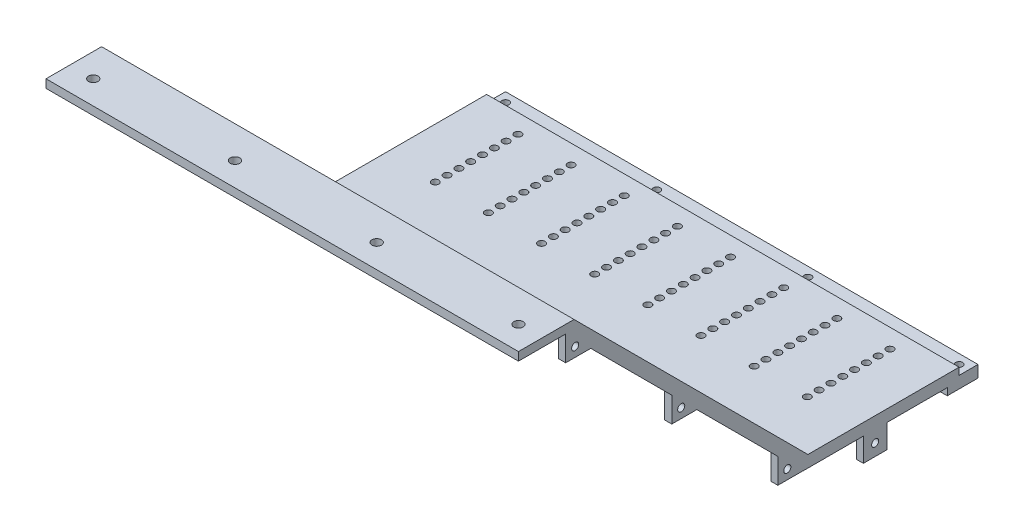
SolidWorks part; units mm, degrees
ref_plane "Front Plane" through (0, 0, 0) normal (0, 0, 1) x (1, 0, 0)
ref_plane "Top Plane" through (0, 0, 0) normal (0, 1, 0) x (1, 0, 0)
ref_plane "Right Plane" through (0, 0, 0) normal (1, 0, 0) x (0, 0, -1)
sketch "Sketch4" plane through (0, 0, 0) normal (1, 0, 0) x (0, 0, -1)
  line L0 (0, 0) -> (-8, 0)
  line L1 (-8, 0) -> (-8, 3)
  line L2 (-8, 3) -> (-72, 3)
  line L3 (-72, 3) -> (-170.9949, 101.9949)
  dimension "D1" = 8
  dimension "D2" = 3
  dimension "D3" = 64
  dimension "D4" = 135
  dimension "D5" = 140
extrude "Extrude-Thin2" add sketch "Sketch4" along normal blind 200 thin thin type one direction reverse wall 5
sketch "Sketch6" plane through (0, 3, 0) normal (0, 1, 0) x (1, 0, 0)
  line L0 (200, -8) -> (200, -72) construction
  line L1 (200, -8) -> (0, -8) construction
  circle A0 centre (178.75, -16) radius 1.5
  dimension "D1" = 3
  dimension "D2" = 21.25
  dimension "D3" = 8
extrude "Cut-Extrude2" cut sketch "Sketch6" against normal up to next
pattern_linear "LPattern1" count 8 spacing 5 along (0, 0, 1) count 8 spacing 22.5 along (-1, 0, 0) of "Cut-Extrude2"
sketch "Sketch7" plane through (0, 0, 0) normal (0, 1, 0) x (1, 0, 0)
  line L0 (200, 0) -> (0, 0) construction
  line L1 (200, 0) -> (200, -8) construction
  circle A0 centre (196, -4) radius 1.5
  dimension "D1" = 3
  dimension "D2" = 4
  dimension "D3" = 4
extrude "Cut-Extrude3" cut sketch "Sketch7" against normal up to next
pattern_linear "LPattern2" count 4 spacing 64 along (-1, 0, 0) of "Cut-Extrude3"
sketch "Sketch8" plane through (0, -34.5, 34.5) normal (0, 0.7071, -0.7071) x (1, 0, 0)
  line L0 (0, -53.033) -> (0, -193.033) construction
  line L1 (17.5, -176.033) -> (182.5, -176.033)
  line L2 (17.5, -176.033) -> (17.5, -70.033)
  line L3 (17.5, -70.033) -> (182.5, -70.033)
  line L4 (182.5, -176.033) -> (182.5, -70.033)
  line L5 (17.5, -176.033) -> (182.5, -70.033) construction
  line L6 (17.5, -70.033) -> (182.5, -176.033) construction
  line L7 (200, -53.033) -> (0, -53.033) construction
  circle A0 centre (19, -180.533) radius 1.5
  circle A1 centre (19, -65.533) radius 1.5
  circle A2 centre (181, -65.533) radius 1.5
  circle A3 centre (181, -180.533) radius 1.5
  point P0 (100, -123.033)
  dimension "D5" = 3
  dimension "D6" = 3
  dimension "D10" = 3
  dimension "D11" = 3
  dimension "D1" = 165
  dimension "D2" = 100
  dimension "D3" = 106
  dimension "D4" = 70
  dimension "D7" = 115
  dimension "D8" = 57.5
  dimension "D9" = 1.5
  dimension "D12" = 1.5
extrude "Cut-Extrude4" cut sketch "Sketch8" against normal up to next
sketch "Sketch9" plane through (200, 0, 0) normal (1, 0, 0) x (0, 0, -1)
  line L0 (-170.9949, 101.9949) -> (-174.5305, 101.9949)
  line L1 (-174.5305, 101.9949) -> (-174.5305, 98.4594)
  line L2 (-174.5305, 98.4594) -> (-170.9949, 101.9949)
extrude "Boss-Extrude1" add sketch "Sketch9" against normal up to surface (200 mm away) up to face at (0, 19.2454, 53.3597)
sketch "Sketch10" plane through (0, 0, 174.5305) normal (0, 0, 1) x (1, 0, 0)
  line L1 (0, 101.9949) -> (200, 101.9949)
  line L2 (0, 101.9949) -> (0, 98.4594)
  line L3 (0, 98.4594) -> (200, 98.4594)
  line L4 (200, 101.9949) -> (200, 98.4594)
extrude "Boss-Extrude2" add sketch "Sketch10" along normal blind 20
sketch "Sketch11" plane through (0, 101.9949, 0) normal (0, 1, 0) x (1, 0, 0)
  line L0 (200, -170.9949) -> (200, -194.5305) construction
  line L1 (200, -194.5305) -> (0, -194.5305) construction
  circle A0 centre (190, -184.5305) radius 2
  dimension "D1" = 4
  dimension "D3" = 10
  dimension "D2" = 10
extrude "Cut-Extrude5" cut sketch "Sketch11" against normal up to next
pattern_linear "LPattern3" count 4 spacing 60 along (-1, 0, 0) of "Cut-Extrude5"
sketch "Sketch12" plane through (200, 0, 0) normal (1, 0, 0) x (0, 0, -1)
  line L0 (-174.5305, 98.4594) -> (-174.5305, 87.8528)
  line L1 (-174.5305, 87.8528) -> (-163.9239, 87.8528)
  line L2 (-74.0711, -2) -> (-174.5305, 98.4594) construction
  line L3 (-174.5305, 98.4594) -> (-163.9239, 87.8528)
  dimension "D1" = 15
extrude "Boss-Extrude3" add sketch "Sketch12" against normal blind 3
sketch "Sketch13" plane through (200, 0, 0) normal (1, 0, 0) x (0, 0, -1)
  line L0 (-174.5305, 87.8528) -> (-163.9239, 87.8528) construction
  line L1 (-174.5305, 98.4594) -> (-174.5305, 87.8528) construction
  circle A0 centre (-170.5305, 91.8528) radius 1.5
  dimension "D1" = 3
  dimension "D2" = 4
  dimension "D3" = 4
extrude "Cut-Extrude6" cut sketch "Sketch13" against normal up to next
pattern_linear "LPattern4" count 3 spacing 63.5 along (0, -0.7071, -0.7071) count 2 spacing 197 along (-1, 0, 0) of "Boss-Extrude3", "Cut-Extrude6"
sketch "Sketch16" plane through (0, -2, 0) normal (0, -1, 0) x (1, 0, 0)
  line L0 (200, 13) -> (200, 74.0711) construction
  line L5 (200, 48.5361) -> (197, 48.5361)
  line L6 (200, 48.5361) -> (200, 38.5361)
  line L7 (200, 38.5361) -> (197, 38.5361)
  line L8 (197, 48.5361) -> (197, 38.5361)
  line L9 (200, 74.0711) -> (0, 74.0711) construction
  dimension "D1" = 3
  dimension "D2" = 10
  dimension "D3" = 25.535
extrude "Boss-Extrude4" add sketch "Sketch16" along normal blind 10
sketch "Sketch17" plane through (200, 0, 0) normal (1, 0, 0) x (0, 0, -1)
  line L0 (-48.5361, -12) -> (-48.5361, -2) construction
  line L1 (-38.5361, -12) -> (-48.5361, -12) construction
  circle A0 centre (-43.5361, -7) radius 1.5
  dimension "D1" = 3
  dimension "D2" = 5
  dimension "D3" = 5
extrude "Cut-Extrude7" cut sketch "Sketch17" against normal up to next
